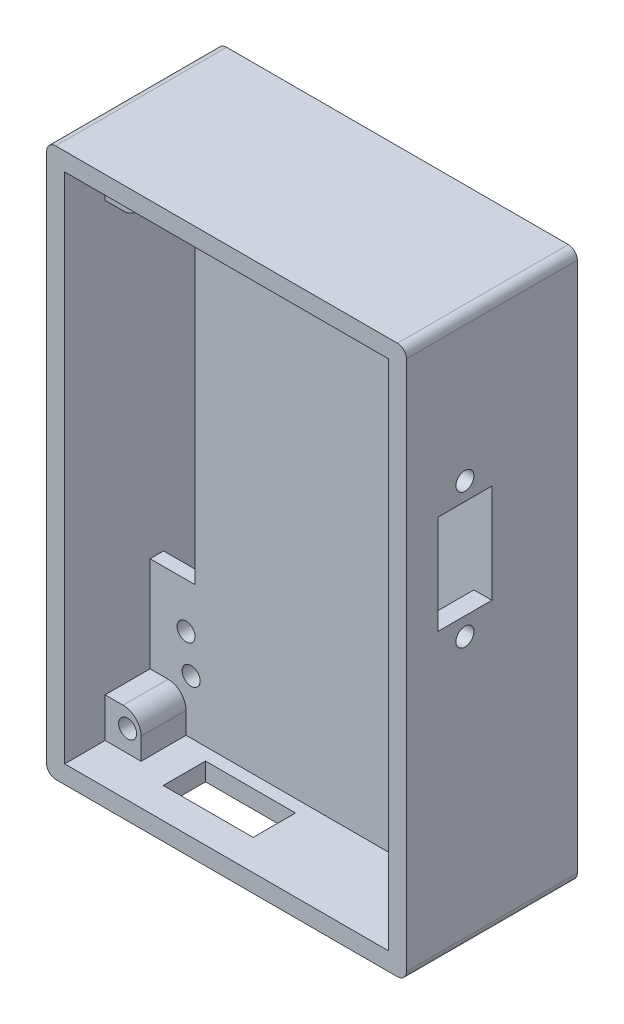
SolidWorks part; units mm, degrees
other "标注1"
sketch "草图16" plane through (38, 59, 11) normal (0.1952, 0.5523, 0.8105) x (0.9731, -0.0061, -0.2302)
other "标注2"
sketch "草图17" plane through (38, 59, 11) normal (0.1952, 0.5523, 0.8105) x (0.9731, -0.0061, -0.2302)
ref_plane "前视基准面" through (0, 0, 0) normal (0, 0, 1) x (1, 0, 0)
ref_plane "上视基准面" through (0, 0, 0) normal (0, 1, 0) x (1, 0, 0)
ref_plane "右视基准面" through (0, 0, 0) normal (1, 0, 0) x (0, 0, -1)
other "Configuration Table"
sketch "草图1" plane through (0, 0, 0) normal (0, 0, 1) x (1, 0, 0)
  line L1 (0, 0) -> (36, 0)
  line L2 (0, 0) -> (0, 57)
  line L3 (0, 57) -> (36, 57)
  line L4 (36, 0) -> (36, 57)
  line L5 (0, 15) -> (5, 15)
  line L6 (0, 15) -> (0, 51)
  line L7 (0, 51) -> (5, 51)
  line L8 (5, 15) -> (5, 51)
  line L9 (-2, 59) -> (-2, -2) construction
  line L10 (28.75, 16) -> (30.25, 16)
  line L11 (38, -2) -> (-2, -2) construction
  line L12 (28.75, 16) -> (28.75, 52)
  line L13 (38, -2) -> (38, 59) construction
  line L15 (38, 59) -> (-2, 59) construction
  line L16 (30.25, 16) -> (30.25, 52)
  line L17 (-1, -2) -> (37, -2)
  line L18 (-2, -1) -> (-2, 58)
  line L19 (-1, 59) -> (37, 59)
  line L20 (38, -1) -> (38, 58)
  line L21 (7.25, 52) -> (28.75, 52)
  line L23 (5.75, 53.5) -> (30.25, 53.5)
  line L24 (30.25, 52) -> (30.25, 53.5)
  line L25 (5.75, 46) -> (7.25, 46)
  line L26 (5.75, 46) -> (5.75, 53.5)
  line L28 (7.25, 46) -> (7.25, 52)
  line L29 (5.75, 16) -> (7.25, 16)
  line L30 (5.75, 16) -> (5.75, 25)
  line L31 (5.75, 25) -> (7.25, 25)
  line L32 (7.25, 16) -> (7.25, 25)
  circle A2 centre (4.56, 6) radius 1
  circle A3 centre (30.56, 6) radius 1
  circle A4 centre (4, 10) radius 1
  circle A5 centre (31, 10) radius 1
  arc A6 (37, -2) -> (38, -1) centre (37, -1) ccw
  arc A7 (-1, -2) -> (-2, -1) centre (-1, -1) cw
  arc A8 (38, 58) -> (37, 59) centre (37, 58) ccw
  arc A9 (-2, 58) -> (-1, 59) centre (-1, 58) cw
  point P20 (-2, -2)
  point P27 (38, -2)
  point P30 (-2, -2)
  point P32 (0, 0)
  point P33 (38, 59)
  point P34 (0, 0)
  point P46 (0, 0)
  point P47 (0, 0)
  point P48 (0, 0)
  point P55 (0, 0)
  point P56 (0, 0)
  point P57 (0, 0)
  point P58 (0, 0)
  dimension "D7" = 4
  dimension "D11" = 1
  dimension "D1" = 36
  dimension "D2" = 57
  dimension "D3" = 2
  dimension "D4" = 2
  dimension "D5" = 2
  dimension "D6" = 2
  dimension "D8" = 5
  dimension "D9" = 4.56
  dimension "D10" = 5.44
  dimension "D12" = 36
  dimension "D13" = 5
  dimension "D14" = 37.5
  dimension "D15" = 1.5
  dimension "D16" = 24.5
  dimension "D17" = 6
  dimension "D19" = 1.5
  dimension "D20" = 21.5
  dimension "D21" = 9
  dimension "D22" = 1.5
  dimension "D23" = 16
sketch "草图2" plane through (0, 0, 0) normal (0, 0, 1) x (1, 0, 0)
  line L7 (0, 0) -> (4, 0)
  line L8 (0, 0) -> (0, 4.4)
  line L9 (0, 4.4) -> (2, 4.4)
  line L10 (0, 0) -> (36, 0) construction
  line L13 (4, 0) -> (4, 2.4)
  line L14 (36, 0) -> (32, 0)
  line L15 (36, 0) -> (36, 4.4)
  line L16 (36, 4.4) -> (34, 4.4)
  line L17 (32, 0) -> (32, 2.4)
  line L18 (36, 57) -> (32, 57)
  line L19 (36, 57) -> (36, 52)
  line L20 (36, 52) -> (34, 52)
  line L21 (32, 57) -> (32, 54)
  line L22 (0, 57) -> (4, 57)
  line L23 (0, 57) -> (0, 52)
  line L24 (0, 52) -> (2, 52)
  line L25 (4, 57) -> (4, 54)
  circle A0 centre (2.5, 2.4) radius 1
  circle A1 centre (34, 2.4) radius 1
  circle A2 centre (2.25, 53.6994) radius 1
  circle A3 centre (33.75, 53.6994) radius 1
  arc A9 (4, 2.4) -> (2, 4.4) centre (2, 2.4) ccw
  arc A10 (34, 4.4) -> (32, 2.4) centre (34, 2.4) ccw
  arc A11 (34, 52) -> (32, 54) centre (34, 54) cw
  arc A12 (2, 52) -> (4, 54) centre (2, 54) ccw
  point P16 (2.0001, 0)
  point P18 (2, 4.3)
  point P25 (3.9, 2.4)
  point P28 (1.9999, 4.2999)
  dimension "D1" = 2
  dimension "D10" = 2
  dimension "D11" = 2
  dimension "D12" = 2
  dimension "D13" = 2
  dimension "D14" = 2
  dimension "D15" = 2
  dimension "D3" = 2.4
  dimension "D4" = 2.4
  dimension "D5" = 31.5
  dimension "D6" = 51.3
  dimension "D7" = 31.5
  dimension "D16" = 4
  dimension "D17" = 5
  dimension "D18" = 5
  dimension "D19" = 4
  dimension "D20" = 4
  dimension "D21" = 4.4
  dimension "D22" = 4.4
  dimension "D23" = 4
  dimension "D24" = 51.3
extrude "螺丝柱" add sketch "草图2" along normal blind 6.5
sketch "ESP32开口" plane through (0, 0, 0) normal (0, 1, 0) x (1, 0, 0)
  line L1 (12.56, 0) -> (22.56, 0)
  line L2 (12.56, 0) -> (12.56, 4.5)
  line L3 (12.56, 4.5) -> (22.56, 4.5)
  line L4 (22.56, 0) -> (22.56, 4.5)
  line L5 (38, 0) -> (-2, 0) construction
  dimension "D1" = 4.5
  dimension "D2" = 10
  dimension "D3" = 0
sketch "草图15" plane through (0, 0, 0) normal (0, -1, 0) x (1, 0, 0)
  line L1 (7.56, 2.9) -> (17.56, 2.9)
  line L2 (7.56, 2.9) -> (7.56, 7.6)
  line L3 (7.56, 7.6) -> (17.56, 7.6)
  line L4 (17.56, 2.9) -> (17.56, 7.6)
extrude "反向螺柱" add sketch "草图2<5>" against normal blind 4.5
sketch "草图2<5>" plane through (0, 0, 0) normal (0, 0, 1) x (1, 0, 0) same geometry as "草图2"
extrude "电源管理板外壳" add sketch "草图1" along normal blind 11 contours L17 L20 L19 L18 L4 L1 L2 L3 region at (-1.1913, -1.1913, 0)
extrude "电源管理板开口" cut sketch "草图15" along normal up to surface (2 mm away) up to face at (18, -2, 5.5)
extrude "ESP32外壳" add sketch "草图1" against normal blind 8 contours L17 L20 L19 L18 L4 L1 L2 L3 region at (-1.1913, -1.1913, 0)
extrude "ESP32" cut sketch "ESP32开口" against normal up to surface (2 mm away) up to face at (18, -2, 5.5)
extrude "底板" add sketch "草图1<29>" along normal blind 1.5 contours L8 L5 L2 L1 L4 L3 L7 A5 A4 A3 A2 L32 L29 L30 L31 L28 L25 L26 L23 L24 L16 L10 L12 L21 region at (19.3937, 27.4594, 0)
sketch "草图1<29>" plane through (0, 0, 0) normal (0, 0, 1) x (1, 0, 0) same geometry as "草图1"
extrude "凸台-拉伸3" add sketch "草图1<30>" against normal blind 2.5 separate body contours L25 L28 L21 L12 L10 L16 L24 L23 L26 | L29 L32 L31 L30 region at (29.1979, 34, 0) region at (6.5, 20.5, 0)
sketch "草图1<30>" plane through (0, 0, 0) normal (0, 0, 1) x (1, 0, 0) same geometry as "草图1"
extrude "凸台-拉伸4" add sketch "草图1<31>" along normal blind 1.5 contours L30 L31 L32 L29 | L12 L21 L28 L25 L26 L23 L24 L16 L10
sketch "草图1<31>" plane through (0, 0, 0) normal (0, 0, 1) x (1, 0, 0) same geometry as "草图1"
sketch "草图18" plane through (38, 0, 0) normal (1, 0, 0) x (0, 0, -1)
  line L1 (-7.5, 30) -> (-1.5, 30)
  line L2 (-7.5, 30) -> (-7.5, 41)
  line L3 (-7.5, 41) -> (-1.5, 41)
  line L4 (-1.5, 30) -> (-1.5, 41)
  circle A0 centre (-4.5, 43) radius 1
  circle A1 centre (-4.5, 28) radius 1
  dimension "D1" = 11
  dimension "D2" = 6
extrude "开关" cut sketch "草图18" against normal up to surface (2 mm away) up to face at (36, 28.35, 6.375)
